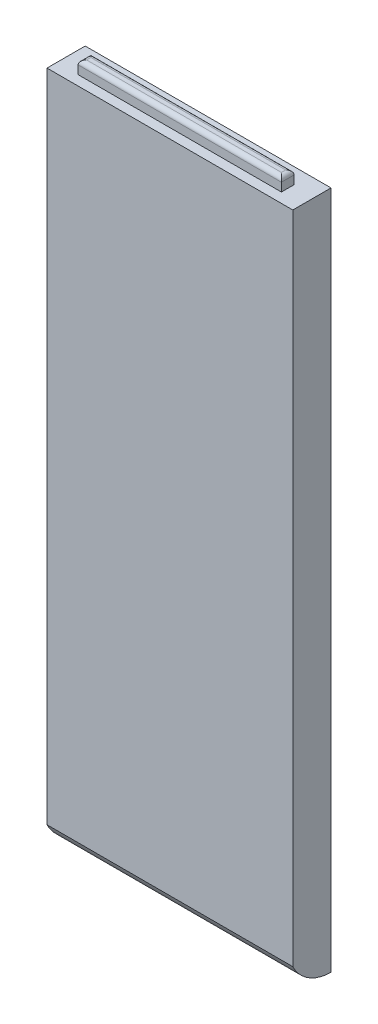
SolidWorks part; units mm, degrees
ref_plane "Front Plane" through (0, 0, 0) normal (0, 0, 1) x (1, 0, 0)
ref_plane "Top Plane" through (0, 0, 0) normal (0, 1, 0) x (1, 0, 0)
ref_plane "Right Plane" through (0, 0, 0) normal (1, 0, 0) x (0, 0, -1)
sketch "Sketch1" plane through (0, 0, 0) normal (0, 0, 1) x (1, 0, 0)
  line L1 (0, 0) -> (57.9, 0)
  line L2 (0, 0) -> (0, 160)
  line L3 (0, 160) -> (57.9, 160)
  line L4 (57.9, 0) -> (57.9, 160)
  dimension "D1" = 160
  dimension "D2" = 57.9
extrude "Boss-Extrude2" add sketch "Sketch1" along normal blind 10
fillet "Fillet2" radius 10 1 edges at (28.95, 0, 10)
sketch "Sketch2" plane through (0, 0, 0) normal (0, 0, -1) x (-1, 0, 0)
  line L0 (-57.9, 0) -> (-57.9, 160) construction
  line L1 (-52.9, 3.65) -> (-5, 3.65)
  line L2 (-52.9, 3.65) -> (-52.9, 1.35)
  line L3 (-52.9, 1.35) -> (-5, 1.35)
  line L4 (-5, 3.65) -> (-5, 1.35)
  line L5 (0, 160) -> (0, 0) construction
  line L6 (0, 0) -> (-57.9, 0) construction
  dimension "D1" = 5
  dimension "D2" = 5
  dimension "D3" = 1.35
  dimension "D4" = 2.3
extrude "Boss-Extrude3" add sketch "Sketch2" along normal blind 3
fillet "Fillet3" radius 1 4 edges at (5, 2.5, -3) (28.95, 1.35, -3) (52.9, 2.5, -3) (28.95, 3.65, -3)
sketch "Sketch4" plane through (0, 160, 0) normal (0, 1, 0) x (1, 0, 0)
  line L0 (0, -10) -> (0, 0) construction
  line L1 (5, -3.6809) -> (52.9, -3.6809)
  line L2 (5, -3.6809) -> (5, -6.6809)
  line L3 (5, -6.6809) -> (52.9, -6.6809)
  line L4 (52.9, -3.6809) -> (52.9, -6.6809)
  line L5 (57.9, -10) -> (57.9, 0) construction
  dimension "D1" = 3
  dimension "D2" = 5
  dimension "D3" = 5
extrude "Boss-Extrude4" add sketch "Sketch4" along normal blind 3
fillet "Fillet4" radius 1 4 edges at (52.9, 163, 5.1809) (28.95, 163, 3.6809) (5, 163, 5.1809) (28.95, 163, 6.6809)
sketch "Sketch5" plane through (0, 0, 10) normal (0, 0, 1) x (1, 0, 0)
  line L1 (0, 160) -> (57.9, 160)
  line L2 (0, 160) -> (0, 0)
  line L3 (0, 0) -> (57.9, 0)
  line L4 (57.9, 160) -> (57.9, 0)
extrude "Cut-Extrude1" cut sketch "Sketch5" against normal blind 1
